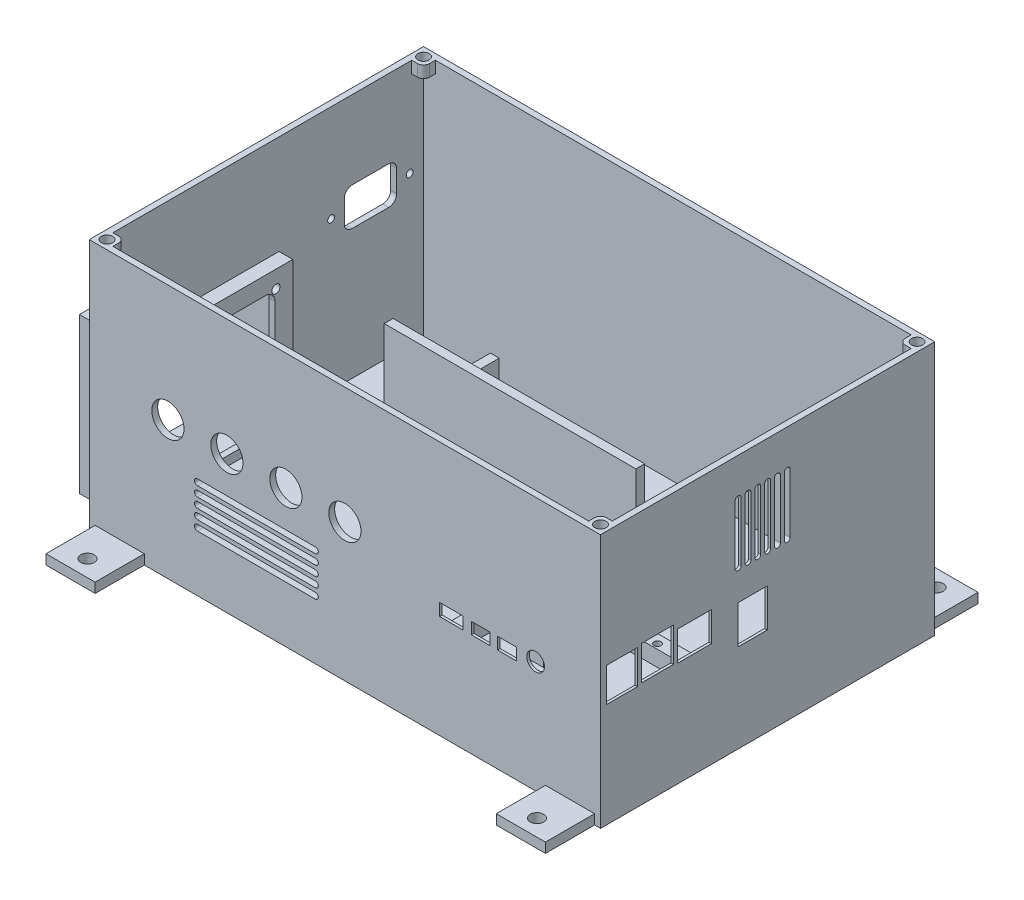
SolidWorks part; units mm, degrees
ref_plane "Front Plane" through (0, 0, 0) normal (0, 0, 1) x (1, 0, 0)
ref_plane "Top Plane" through (0, 0, 0) normal (0, 1, 0) x (1, 0, 0)
ref_plane "Right Plane" through (0, 0, 0) normal (1, 0, 0) x (0, 0, -1)
sketch "Sketch1" plane through (0, 0, 0) normal (0, 1, 0) x (1, 0, 0)
  line L1 (-130, -85) -> (130, -85)
  line L2 (-130, -85) -> (-130, 85)
  line L3 (-130, 85) -> (130, 85)
  line L4 (130, -85) -> (130, 85)
  line L5 (-130, -85) -> (130, 85) construction
  line L6 (-130, 85) -> (130, -85) construction
  point P0 (0, 0)
  dimension "D1" = 170
  dimension "D2" = 260
extrude "Floor" add sketch "Sketch1" along normal blind 4.3805
sketch "Sketch2" plane through (0, 4.3805, 0) normal (0, 1, 0) x (1, 0, 0)
  line L0 (127, -82) -> (127, 82)
  line L1 (127, 82) -> (-127, 82)
  line L2 (-127, 82) -> (-127, -82)
  line L3 (-127, -82) -> (127, -82)
  line L4 (130, -85) -> (130, 85)
  line L5 (130, 85) -> (-130, 85)
  line L6 (-130, 85) -> (-130, -85)
  line L7 (-130, -85) -> (130, -85)
  line L8 (130, -85) -> (130, 85)
  line L9 (130, 85) -> (-130, 85)
  line L10 (-130, 85) -> (-130, -85)
  line L11 (-130, -85) -> (130, -85)
  dimension "D1" = 0
  dimension "D2" = 3
extrude "Wall" add sketch "Sketch2" along normal blind 125
sketch "Sketch4" plane through (0, 4.3805, 0) normal (0, 1, 0) x (1, 0, 0)
  line L0 (120, -33) -> (49, -33)
  line L1 (127, -82) -> (42, -82)
  line L2 (127, -82) -> (127, -26)
  line L3 (127, -26) -> (42, -26)
  line L4 (42, -82) -> (42, -26)
  line L5 (49, -75) -> (49, -33)
  line L6 (120, -75) -> (49, -75)
  line L7 (120, -75) -> (120, -33)
  dimension "D1" = 85
  dimension "D2" = 56
  dimension "D3" = 7
extrude "Rpi stand" add sketch "Sketch4" along normal blind 8 from offset 29
sketch "Sketch7" plane through (0, 129.3805, 0) normal (0, 1, 0) x (1, 0, 0)
sketch "Sketch3" plane through (0, 0, 0) normal (0, 1, 0) x (1, 0, 0)
  line L0 (-114.3, 101.6) -> (114.3, 101.6) construction
  line L1 (-127, 85) -> (-102, 85)
  line L2 (-127, 85) -> (-127, 110)
  line L3 (-127, 110) -> (-102, 110)
  line L4 (-102, 85) -> (-102, 110)
  line L5 (127, 85) -> (102, 85)
  line L6 (127, 85) -> (127, 110)
  line L7 (127, 110) -> (102, 110)
  line L8 (102, 85) -> (102, 110)
  line L9 (-127, -85) -> (-102, -85)
  line L10 (-127, -85) -> (-127, -110)
  line L11 (-127, -110) -> (-102, -110)
  line L12 (-102, -85) -> (-102, -110)
  line L13 (127, -85) -> (102, -85)
  line L14 (127, -85) -> (127, -110)
  line L15 (127, -110) -> (102, -110)
  line L16 (102, -85) -> (102, -110)
  line L17 (114.3, 101.6) -> (114.3, -101.6) construction
  line L18 (114.3, -101.6) -> (-114.3, -101.6) construction
  line L19 (-114.3, -101.6) -> (-114.3, 101.6) construction
  line L20 (-130, 0) -> (130, 0) construction
  line L21 (130, 85) -> (-130, 85) construction
  line L22 (130, -85) -> (130, 85) construction
  line L23 (0, 101.6) -> (0, -101.6) construction
  line L26 (-130, 85) -> (-130, -85) construction
  line L27 (-130, -85) -> (130, -85) construction
  circle A0 centre (-114.3, 101.6) radius 3.429
  circle A1 centre (114.3, 101.6) radius 3.429
  circle A2 centre (114.3, -101.6) radius 3.429
  circle A3 centre (-114.3, -101.6) radius 3.429
  point P4 (-130, -85)
  point P9 (130, -85)
  point P28 (-114.5, -85)
  point P29 (-102, -97.5)
  point P30 (114.5, -85)
  point P31 (-102, 97.5)
  dimension "D5" = 6.858
  dimension "D1" = 25
  dimension "D2" = 25
  dimension "D3" = 25
  dimension "D6" = 203.2
  dimension "D7" = 228.6
  dimension "D8" = 3
  dimension "D9" = 3
  dimension "D4" = 25
extrude "Brackets" add sketch "Sketch3" along normal blind 5
sketch "Sketch5" plane through (-130, 0, 0) normal (-1, 0, 0) x (0, 0, 1)
  line L0 (-8.5, 78.8805) -> (70, 78.8805)
  line L1 (-1, 4.3805) -> (62.5, 4.3805)
  line L2 (-4.5, 7.8805) -> (-4.5, 71.3805)
  line L3 (-1, 74.8805) -> (62.5, 74.8805)
  line L4 (66, 7.8805) -> (66, 71.3805)
  line L5 (70, 0.3805) -> (70, 78.8805)
  line L6 (-8.5, 0.3805) -> (70, 0.3805)
  line L7 (-8.5, 0.3805) -> (-8.5, 78.8805)
  line L8 (-4.5, 4.3805) -> (66, 4.3805) construction
  line L9 (110, 5) -> (110, 0) construction
  line L10 (-4.5, 4.3805) -> (-4.5, 74.8805) construction
  line L11 (-82, 4.3805) -> (82, 4.3805) construction
  line L12 (66, 4.3805) -> (66, 74.8805) construction
  line L13 (-4.5, 74.8805) -> (66, 74.8805) construction
  arc A0 (-1, 4.3805) -> (-4.5, 7.8805) centre (-1, 7.8805) cw
  arc A1 (62.5, 4.3805) -> (66, 7.8805) centre (62.5, 7.8805) ccw
  arc A2 (62.5, 74.8805) -> (66, 71.3805) centre (62.5, 71.3805) cw
  arc A3 (-4.5, 71.3805) -> (-1, 74.8805) centre (-1, 71.3805) cw
  dimension "D4" = 3.5
  dimension "D1" = 70.5
  dimension "D2" = 70.5
  dimension "D5" = 40
  dimension "D3" = 4
extrude "Fan Holder" add sketch "Sketch5" along normal blind 20 and the other way blind 10
sketch "Sketch31" plane through (0, 0.3805, 0) normal (0, -1, 0) x (1, 0, 0)
  line L4 (-130, -8.5) -> (-130, 70)
  line L5 (-130, 70) -> (-150, 70)
  line L6 (-150, 70) -> (-150, -8.5)
  line L7 (-150, -8.5) -> (-130, -8.5)
  line L8 (-130, -8.5) -> (-130, 70)
  line L9 (-130, 70) -> (-150, 70)
  line L10 (-150, 70) -> (-150, -8.5)
  line L11 (-150, -8.5) -> (-130, -8.5)
  dimension "D1" = 0
extrude "Bring fan holder to ground" add sketch "Sketch31" along normal up to surface (0.3805 mm away) up to face at (0, 0, 0)
sketch "Sketch8" plane through (-130, 0, 0) normal (-1, 0, 0) x (0, 0, 1)
  line L4 (-4.5, 71.3805) -> (-4.5, 7.8805)
  line L5 (-1, 4.3805) -> (62.5, 4.3805)
  line L6 (66, 7.8805) -> (66, 71.3805)
  line L7 (62.5, 74.8805) -> (-1, 74.8805)
  line L8 (-4.5, 71.3805) -> (-4.5, 7.8805)
  line L9 (-1, 4.3805) -> (62.5, 4.3805)
  line L10 (66, 7.8805) -> (66, 71.3805)
  line L23 (62.5, 74.8805) -> (-1, 74.8805)
  arc A2 (-4.5, 7.8805) -> (-1, 4.3805) centre (-1, 7.8805) ccw
  arc A3 (-4.5, 7.8805) -> (-1, 4.3805) centre (-1, 7.8805) ccw
  arc A4 (62.5, 4.3805) -> (66, 7.8805) centre (62.5, 7.8805) ccw
  arc A5 (62.5, 4.3805) -> (66, 7.8805) centre (62.5, 7.8805) ccw
  arc A8 (66, 71.3805) -> (62.5, 74.8805) centre (62.5, 71.3805) ccw
  arc A14 (66, 71.3805) -> (62.5, 74.8805) centre (62.5, 71.3805) ccw
  arc A16 (-1, 74.8805) -> (-4.5, 71.3805) centre (-1, 71.3805) ccw
  arc A17 (-1, 74.8805) -> (-4.5, 71.3805) centre (-1, 71.3805) ccw
  dimension "D1" = 0
extrude "Fan hole" cut sketch "Sketch8" against normal up to next
sketch "Sketch11" plane through (-120, 0, 0) normal (-1, 0, 0) x (0, 0, 1)
  line L0 (-8.5, 39.4402) -> (70, 39.4402) construction
  line L1 (30.75, 78.8805) -> (30.75, 0.3805) construction
  line L3 (0.05, 8.7402) -> (61.45, 8.7402) construction
  line L4 (-8.5, 78.8805) -> (-8.5, 0)
  line L5 (-8.5, 0) -> (70, 0)
  line L6 (70, 0) -> (70, 78.8805)
  line L7 (70, 78.8805) -> (-8.5, 78.8805)
  line L8 (-8.5, 78.8805) -> (-8.5, 0)
  line L10 (70, 0) -> (70, 78.8805)
  line L11 (70, 78.8805) -> (-8.5, 78.8805)
  line L12 (0.05, 8.7402) -> (0.05, 70.1402) construction
  line L13 (0.05, 70.1402) -> (61.45, 70.1402) construction
  line L14 (61.45, 8.7402) -> (61.45, 70.1402) construction
  line L15 (0.05, 8.7402) -> (61.45, 70.1402) construction
  line L16 (0.5, 69.8805) -> (0.5, 9)
  line L17 (0.5, 9) -> (61, 9)
  line L18 (61, 9) -> (61, 69.8805)
  line L19 (61, 69.8805) -> (0.5, 69.8805)
  line L20 (0.5, 64.8805) -> (0.5, 14)
  line L22 (61, 14) -> (61, 64.8805)
  line L23 (56, 69.8805) -> (5.5, 69.8805)
  line L24 (0.05, 70.1402) -> (61.45, 8.7402) construction
  line L29 (5.5, 9) -> (56, 9)
  line L31 (-8.5, 0) -> (70, 0)
  arc A0 (0.5, 14) -> (5.5, 9) centre (5.5, 14) ccw
  arc A1 (56, 9) -> (61, 14) centre (56, 14) ccw
  arc A2 (61, 64.8805) -> (56, 69.8805) centre (56, 64.8805) ccw
  arc A3 (0.5, 64.8805) -> (5.5, 69.8805) centre (5.5, 64.8805) cw
  circle A4 centre (0.05, 70.1402) radius 2.1
  circle A5 centre (61.45, 70.1402) radius 2.1
  circle A6 centre (61.45, 8.7402) radius 2.1
  circle A7 centre (0.05, 8.7402) radius 2.1
  point P4 (54.4258, 8.7402)
  point P24 (30.75, 39.4402)
  point P33 (0.5, 21.4808)
  point P34 (30.75, 39.4402)
  point P35 (8.0648, 8.7402)
  point P37 (8.0648, 9.4667)
  point P39 (54.4258, 9.4667)
  dimension "D3" = 5
  dimension "D6" = 4.2
  dimension "D4" = 61.4
  dimension "D5" = 61.4
  dimension "D1" = 0
  dimension "D2" = 9
extrude "Boss-Extrude9" add sketch "Sketch11" along normal blind 3
sketch "Sketch12" plane through (0, 33.3805, 0) normal (0, -1, 0) x (1, 0, 0)
  line L1 (42, 26) -> (49, 26)
  line L2 (42, 26) -> (42, 33)
  line L3 (42, 33) -> (49, 33)
  line L4 (49, 26) -> (49, 33)
  dimension "D1" = 7
  dimension "D2" = 7
extrude "Boss-Extrude10" add sketch "Sketch12" along normal up to next
sketch "Sketch13" plane through (0, 4.3805, 0) normal (0, 1, 0) x (1, 0, 0)
  line L0 (127, 82) -> (-127, 82) construction
  line L2 (-107, -57) -> (-107, 5.7) construction
  line L3 (-107, 5.7) -> (-69.4, 5.7) construction
  line L4 (-107, -57) -> (-69.4, -57) construction
  line L5 (-69.4, 5.7) -> (-69.4, -57) construction
  line L6 (-69.4, 5.7) -> (-57.4, 5.7) construction
  line L7 (-57.4, 5.7) -> (-57.4, -57) construction
  line L8 (-57.4, -57) -> (-19.8, -57) construction
  line L9 (-19.8, -57) -> (-19.8, 5.7) construction
  line L10 (-19.8, 5.7) -> (-57.4, 5.7) construction
  line L11 (-69.4, -57) -> (-57.4, -57) construction
  line L12 (-19.8, -57) -> (62.83, -57) construction
  line L13 (62.83, -57) -> (62.83, -25.4) construction
  line L14 (62.83, -25.4) -> (105, -25.4) construction
  line L15 (105, -25.4) -> (105, -57) construction
  line L16 (105, -57) -> (62.83, -57) construction
  line L17 (118, 82) -> (118, 21.5) construction
  line L18 (-16.3, -57.85) -> (-16.3, 6.55) construction
  line L20 (127, -82) -> (127, 82) construction
  line L21 (118, 21.5) -> (120.7, 21.5) construction
  line L22 (118, 21.5) -> (41.5, 21.5) construction
  line L23 (-6.3, -47) -> (30.69, -47) construction
  line L24 (-6.3, -47) -> (-6.3, -6.4) construction
  line L25 (-6.3, -6.4) -> (30.69, -6.4) construction
  line L26 (30.69, -47) -> (30.69, -6.4) construction
  line L27 (-6.3, -47) -> (30.69, -6.4) construction
  line L28 (-6.3, -6.4) -> (30.69, -47) construction
  line L29 (130, -85) -> (130, 85) construction
  line L30 (-127, -82) -> (127, -82) construction
  line L457 (-127, 8.5) -> (-127, -70) construction
  line L458 (-127, -82) -> (127, -82) construction
  circle A0 centre (-107, -57) radius 1.25
  circle A1 centre (-107, 5.7) radius 1.25
  circle A2 centre (-69.4, 5.7) radius 1.25
  circle A3 centre (-69.4, -57) radius 1.25
  circle A4 centre (-57.4, 5.7) radius 1.25
  circle A5 centre (-57.4, -57) radius 1.25
  circle A6 centre (-19.8, -57) radius 1.25
  circle A7 centre (-19.8, 5.7) radius 1.25
  circle A12 centre (120.7, 21.5) radius 1.25
  circle A13 centre (41.5, 21.5) radius 1.25
  circle A14 centre (-107, 5.7) radius 2.75
  circle A15 centre (-107, -57) radius 2.75
  circle A16 centre (-69.4, 5.7) radius 2.75
  circle A17 centre (-57.4, 5.7) radius 2.75
  circle A18 centre (-69.4, -57) radius 2.75
  circle A19 centre (-57.4, -57) radius 2.75
  circle A20 centre (-19.8, -57) radius 2.75
  circle A21 centre (-19.8, 5.7) radius 2.75
  circle A22 centre (62.83, -57) radius 2.5
  circle A23 centre (62.83, -25.4) radius 2.5
  circle A24 centre (105, -25.4) radius 2.5
  circle A25 centre (105, -57) radius 2.5
  circle A26 centre (-6.3, -47) radius 1.25
  circle A28 centre (-6.3, -47) radius 2.75
  circle A30 centre (-69.4, 5.7) radius 1.65 construction
  circle A31 centre (104.2333, -41.2) radius 1.5 construction
  circle A32 centre (104.2333, -41.2) radius 1.5 construction
  circle A33 centre (63.5933, -41.2) radius 1.5 construction
  circle A34 centre (63.5933, -41.2) radius 1.5 construction
  circle A35 centre (104.2333, -41.2) radius 3
  circle A36 centre (63.5933, -41.2) radius 3
  circle A37 centre (-6.3, -6.4) radius 1.25
  circle A38 centre (30.69, -6.4) radius 1.25
  circle A39 centre (30.69, -47) radius 1.25
  circle A40 centre (-6.3, -6.4) radius 2.75
  circle A41 centre (30.69, -6.4) radius 2.75
  circle A42 centre (30.69, -47) radius 2.75
  circle A43 centre (30.69, -6.4) radius 1.5 construction
  circle A44 centre (30.69, -6.4) radius 1.5 construction
  point P2 (-127, -82)
  point P3 (127, -82)
  point P8 (12.195, -26.7)
  point P31 (127, 82)
  point P32 (-127, 82)
  point P90 (-123, -62.5)
  point P91 (-123, -66)
  point P92 (-130, -70)
  point P93 (-130, 8.5)
  point P94 (-127, 8.5)
  point P95 (-127, -70)
  point P96 (-127, 8.5)
  point P97 (-120, 8.5)
  point P98 (-120, -70)
  point P99 (-127, -70)
  point P100 (-120, 8.5)
  point P101 (-120, -70)
  point P102 (-130, -85)
  point P103 (-127, -85)
  point P104 (-102, -85)
  point P105 (102, -85)
  point P106 (127, -85)
  point P107 (130, -85)
  point P108 (-130, 85)
  point P109 (-130, -85)
  point P110 (130, 85)
  point P111 (127, 85)
  point P112 (102, 85)
  point P113 (-102, 85)
  point P114 (-127, 85)
  point P115 (-130, 85)
  point P116 (130, -85)
  point P117 (130, 85)
  point P118 (-130, 85)
  point P119 (-130, -85)
  point P120 (130, 85)
  point P121 (-130, 85)
  point P122 (130, -85)
  point P123 (130, 85)
  point P124 (-130, -85)
  point P125 (130, -85)
  point P126 (-127, 82)
  point P127 (-127, -82)
  point P128 (127, 82)
  point P129 (-127, 82)
  point P130 (127, -82)
  point P131 (127, 82)
  point P132 (-127, -82)
  point P133 (127, -82)
  point P134 (-127, 82)
  point P135 (-127, 8.5)
  point P136 (-127, -70)
  point P137 (-127, -82)
  point P138 (127, -82)
  point P139 (127, 82)
  point P140 (42, -82)
  point P141 (127, -82)
  point P142 (42, -26)
  point P143 (42, -82)
  point P144 (127, -26)
  point P145 (42, -26)
  point P146 (127, -82)
  point P147 (127, -26)
  point P148 (42, -82)
  point P149 (127, -82)
  point P150 (42, -33)
  point P151 (42, -82)
  point P152 (127, -26)
  point P153 (49, -26)
  point P154 (127, -82)
  point P155 (127, -26)
  point P156 (49, -75)
  point P157 (120, -75)
  point P158 (49, -33)
  point P159 (49, -75)
  point P160 (120, -33)
  point P161 (49, -33)
  point P162 (120, -75)
  point P163 (120, -33)
  point P164 (49, -75)
  point P165 (120, -75)
  point P166 (49, -33)
  point P167 (49, -75)
  point P168 (120, -33)
  point P169 (49, -33)
  point P170 (120, -75)
  point P171 (120, -33)
  point P172 (-102, 110)
  point P173 (-127, 110)
  point P174 (-102, 85)
  point P175 (-102, 110)
  point P176 (-127, 85)
  point P177 (-102, 85)
  point P178 (-127, 110)
  point P179 (-127, 85)
  point P180 (-102, 110)
  point P181 (-127, 110)
  point P182 (-102, 85)
  point P183 (-102, 110)
  point P184 (-127, 110)
  point P185 (-127, 85)
  point P186 (-114.3, 101.6)
  point P187 (-111.0208, 102.6025)
  point P188 (-114.3, 101.6)
  point P189 (-111.0208, 102.6025)
  point P190 (114.3, 101.6)
  point P191 (117.5792, 102.6025)
  point P192 (114.3, 101.6)
  point P193 (117.5792, 102.6025)
  point P194 (127, 85)
  point P195 (127, 110)
  point P196 (127, 110)
  point P197 (102, 110)
  point P198 (102, 110)
  point P199 (102, 85)
  point P200 (127, 85)
  point P201 (127, 110)
  point P202 (127, 110)
  point P203 (102, 110)
  point P204 (102, 110)
  point P205 (102, 85)
  point P206 (102, 85)
  point P207 (127, 85)
  point P208 (-114.3, -101.6)
  point P209 (-111.0208, -100.5975)
  point P210 (-114.3, -101.6)
  point P211 (-111.0208, -100.5975)
  point P212 (-127, -85)
  point P213 (-127, -110)
  point P214 (-127, -110)
  point P215 (-102, -110)
  point P216 (-102, -110)
  point P217 (-102, -85)
  point P218 (-127, -85)
  point P219 (-127, -110)
  point P220 (-127, -110)
  point P221 (-102, -110)
  point P222 (-102, -110)
  point P223 (-102, -85)
  point P224 (-102, -85)
  point P225 (-127, -85)
  point P226 (114.3, -101.6)
  point P227 (117.5792, -100.5975)
  point P228 (114.3, -101.6)
  point P229 (117.5792, -100.5975)
  point P230 (127, -110)
  point P231 (127, -85)
  point P232 (102, -85)
  point P233 (102, -110)
  point P234 (102, -110)
  point P235 (127, -110)
  point P236 (127, -110)
  point P237 (127, -85)
  point P238 (127, -85)
  point P239 (102, -85)
  point P240 (102, -85)
  point P241 (102, -110)
  point P242 (102, -110)
  point P243 (127, -110)
  point P244 (-130, 8.5)
  point P245 (-130, -70)
  point P246 (-120, 8.5)
  point P247 (-127, 8.5)
  point P248 (-130, 8.5)
  point P249 (-150, 8.5)
  point P250 (-120, -70)
  point P251 (-127, -70)
  point P252 (-130, -70)
  point P253 (-150, -70)
  point P254 (-130, -70)
  point P255 (-150, -70)
  point P256 (-130, 8.5)
  point P257 (-150, 8.5)
  point P258 (-120, -70)
  point P259 (-120, 8.5)
  point P260 (-123, 4.5)
  point P261 (-150, 4.5)
  point P262 (-123, 4.5)
  point P263 (-150, 4.5)
  point P264 (-123, 1)
  point P265 (-150, 1)
  point P266 (-123, -62.5)
  point P267 (-150, -62.5)
  point P268 (-123, -66)
  point P269 (-150, -66)
  point P270 (-123, -66)
  point P271 (-150, -66)
  point P272 (-123, -62.5)
  point P273 (-150, -62.5)
  point P274 (-123, 1)
  point P275 (-150, 1)
  point P276 (-150, -70)
  point P277 (-150, 8.5)
  point P278 (-150, 8.5)
  point P279 (-150, -70)
  point P280 (-150, 4.5)
  point P281 (-150, 1)
  point P282 (-150, -62.5)
  point P283 (-150, 1)
  point P284 (-150, -62.5)
  point P285 (-150, -66)
  point P286 (-150, -62.5)
  point P287 (-150, -66)
  point P288 (-150, 1)
  point P289 (-150, -62.5)
  point P290 (-150, 4.5)
  point P291 (-150, 1)
  point P292 (-123, 4.5)
  point P293 (-123, 1)
  point P294 (-123, -62.5)
  point P295 (-123, 1)
  point P296 (-123, 4.5)
  point P297 (-123, 1)
  point P298 (-123, 1)
  point P299 (-123, -62.5)
  point P300 (-123, -62.5)
  point P301 (-123, -66)
  point P302 (-123, -5.5)
  point P303 (-120, -5.5)
  point P304 (-123, -56)
  point P305 (-120, -56)
  point P306 (-123, -61)
  point P307 (-120, -61)
  point P308 (-123, -61)
  point P309 (-120, -61)
  point P310 (-123, -56)
  point P311 (-120, -56)
  point P312 (-123, -5.5)
  point P313 (-120, -5.5)
  point P314 (-123, -0.5)
  point P315 (-120, -0.5)
  point P316 (-123, -0.5)
  point P317 (-120, -0.5)
  point P318 (-123, -0.5)
  point P319 (-123, -5.5)
  point P320 (-123, -56)
  point P321 (-123, -5.5)
  point P322 (-123, -56)
  point P323 (-123, -61)
  point P324 (-123, -56)
  point P325 (-123, -61)
  point P326 (-123, -5.5)
  point P327 (-123, -56)
  point P328 (-123, -0.5)
  point P329 (-123, -5.5)
  point P330 (-120, -5.5)
  point P331 (-120, -0.5)
  point P332 (-120, -56)
  point P333 (-120, -5.5)
  point P334 (-120, -61)
  point P335 (-120, -56)
  point P336 (-120, -61)
  point P337 (-120, -56)
  point P338 (-120, -5.5)
  point P339 (-120, -56)
  point P340 (-120, -5.5)
  point P341 (-120, -0.5)
  point P342 (-123, 2.05)
  point P343 (-123, -2.15)
  point P344 (-120, -2.15)
  point P345 (-120, 2.05)
  point P346 (-123, -59.35)
  point P347 (-123, -63.55)
  point P348 (-120, -63.55)
  point P349 (-120, -59.35)
  point P350 (-123, -59.35)
  point P351 (-123, -63.55)
  point P352 (-120, -63.55)
  point P353 (-120, -59.35)
  point P354 (-123, 2.05)
  point P355 (-123, -2.15)
  point P356 (-120, -2.15)
  point P357 (-120, 2.05)
  point P358 (49, -33)
  point P359 (42, -33)
  point P360 (49, -26)
  point P361 (49, -33)
  point P362 (42, -33)
  point P363 (42, -26)
  point P364 (42, -26)
  point P365 (49, -26)
  point P366 (49, -26)
  point P367 (49, -33)
  point P368 (49, -33)
  point P369 (42, -33)
  point P370 (-130, -85)
  point P371 (130, -85)
  point P372 (-130, -85)
  point P373 (-130, 85)
  point P374 (-130, 85)
  point P375 (130, 85)
  point P376 (130, -85)
  point P377 (130, 85)
  point P378 (-130, -85)
  point P379 (130, 85)
  point P380 (-130, 85)
  point P381 (130, -85)
  point P382 (127, -82)
  point P383 (127, 82)
  point P384 (127, 82)
  point P385 (-127, 82)
  point P386 (-127, 82)
  point P387 (-127, -82)
  point P388 (-127, -82)
  point P389 (127, -82)
  point P390 (130, -85)
  point P391 (130, 85)
  point P392 (130, 85)
  point P393 (-130, 85)
  point P394 (-130, 85)
  point P395 (-130, -85)
  point P396 (-130, -85)
  point P397 (130, -85)
  point P398 (130, -85)
  point P399 (130, 85)
  point P400 (130, 85)
  point P401 (-130, 85)
  point P402 (-130, 85)
  point P403 (-130, -85)
  point P404 (-130, -85)
  point P405 (130, -85)
  point P406 (120, -33)
  point P407 (49, -33)
  point P408 (127, -82)
  point P409 (42, -82)
  point P410 (127, -82)
  point P411 (127, -26)
  point P412 (127, -26)
  point P413 (42, -26)
  point P414 (42, -82)
  point P415 (42, -26)
  point P416 (49, -75)
  point P417 (49, -33)
  point P418 (120, -75)
  point P419 (49, -75)
  point P420 (120, -75)
  point P421 (120, -33)
  point P422 (-114.3, 101.6)
  point P423 (114.3, 101.6)
  point P424 (-127, 85)
  point P425 (-102, 85)
  point P426 (-127, 85)
  point P427 (-127, 110)
  point P428 (-127, 110)
  point P429 (-102, 110)
  point P430 (-102, 85)
  point P431 (-102, 110)
  point P432 (127, 85)
  point P433 (102, 85)
  point P434 (127, 85)
  point P435 (127, 110)
  point P436 (127, 110)
  point P437 (102, 110)
  point P438 (102, 85)
  point P439 (102, 110)
  point P440 (-127, -85)
  point P441 (-102, -85)
  point P442 (-127, -85)
  point P443 (-127, -110)
  point P444 (-127, -110)
  point P445 (-102, -110)
  point P446 (-102, -85)
  point P447 (-102, -110)
  point P448 (127, -85)
  point P449 (102, -85)
  point P450 (127, -85)
  point P451 (127, -110)
  point P452 (127, -110)
  point P453 (102, -110)
  point P454 (102, -85)
  point P455 (102, -110)
  point P456 (114.3, 101.6)
  point P457 (114.3, -101.6)
  point P458 (114.3, -101.6)
  point P459 (-114.3, -101.6)
  point P460 (-114.3, -101.6)
  point P461 (-114.3, 101.6)
  point P462 (-130, 0)
  point P463 (130, 0)
  point P464 (130, 85)
  point P465 (-130, 85)
  point P466 (130, -85)
  point P467 (130, 85)
  point P468 (0, 101.6)
  point P469 (0, -101.6)
  point P470 (-130, 85)
  point P471 (-130, -85)
  point P472 (-130, -85)
  point P473 (130, -85)
  point P474 (-130, 8.5)
  point P475 (-130, -70)
  point P476 (-130, 1)
  point P477 (-130, -62.5)
  point P478 (-130, 1)
  point P479 (-130, -62.5)
  point P480 (-130, 8.5)
  point P481 (-130, -70)
  point P482 (-130, 4.5)
  point P483 (-130, -66)
  point P484 (-130, 82)
  point P485 (-130, -82)
  point P486 (-130, 4.5)
  point P487 (-130, -66)
  point P488 (-130, 1)
  point P489 (-130, -62.5)
  point P490 (-130, -62.5)
  point P491 (-130, 1)
  point P492 (-130, 1)
  point P493 (-130, -62.5)
  point P494 (-130, -62.5)
  point P495 (-130, 1)
  point P496 (-120, 8.5)
  point P497 (-120, -70)
  point P498 (-120, -0.05)
  point P499 (-120, -61.45)
  point P500 (-120, 8.5)
  point P501 (-120, -70)
  point P502 (-120, -70)
  point P503 (-120, 8.5)
  point P504 (-120, 8.5)
  point P505 (-120, -70)
  point P506 (-120, -70)
  point P507 (-120, 8.5)
  point P508 (-120, -0.05)
  point P509 (-120, -61.45)
  point P510 (-120, -0.05)
  point P511 (-120, -61.45)
  point P512 (-120, -0.5)
  point P513 (-120, -61)
  point P514 (-120, -61)
  point P515 (-120, -0.5)
  point P516 (-120, -5.5)
  point P517 (-120, -56)
  point P518 (-120, -56)
  point P519 (-120, -5.5)
  point P520 (-120, -0.05)
  point P521 (-120, -61.45)
  point P522 (42, -26)
  point P523 (49, -26)
  point P524 (42, -26)
  point P525 (42, -33)
  point P526 (42, -33)
  point P527 (49, -33)
  point P528 (49, -26)
  point P529 (49, -33)
  point P530 (-123, -62.5)
  point P531 (-123, -66)
  point P532 (-130, -70)
  point P533 (-130, 8.5)
  point P534 (-127, 8.5)
  point P535 (-127, -70)
  point P536 (-127, 8.5)
  point P537 (-120, 8.5)
  point P538 (-120, -70)
  point P539 (-127, -70)
  point P540 (-120, 8.5)
  point P541 (-120, -70)
  point P542 (-130, -85)
  point P543 (-127, -85)
  point P544 (-102, -85)
  point P545 (102, -85)
  point P546 (127, -85)
  point P547 (130, -85)
  point P548 (-130, 85)
  point P549 (-130, -85)
  point P550 (130, 85)
  point P551 (127, 85)
  point P552 (102, 85)
  point P553 (-102, 85)
  point P554 (-127, 85)
  point P555 (-130, 85)
  point P556 (130, -85)
  point P557 (130, 85)
  point P558 (-130, 85)
  point P559 (-130, -85)
  point P560 (130, 85)
  point P561 (-130, 85)
  point P562 (130, -85)
  point P563 (130, 85)
  point P564 (-130, -85)
  point P565 (130, -85)
  point P566 (-127, 82)
  point P567 (-127, -82)
  point P568 (127, 82)
  point P569 (-127, 82)
  point P570 (127, -82)
  point P571 (127, 82)
  point P572 (-127, -82)
  point P573 (127, -82)
  point P574 (-127, 82)
  point P575 (-127, 8.5)
  point P576 (-127, -70)
  point P577 (-127, -82)
  point P578 (127, 82)
  point P579 (-127, 82)
  point P580 (127, -82)
  point P581 (127, 82)
  point P582 (-127, -82)
  point P583 (127, -82)
  point P584 (42, -82)
  point P585 (127, -82)
  point P586 (42, -26)
  point P587 (42, -82)
  point P588 (127, -26)
  point P589 (42, -26)
  point P590 (127, -82)
  point P591 (127, -26)
  point P592 (42, -82)
  point P593 (127, -82)
  point P594 (42, -33)
  point P595 (42, -82)
  point P596 (127, -26)
  point P597 (49, -26)
  point P598 (127, -82)
  point P599 (127, -26)
  point P600 (49, -75)
  point P601 (120, -75)
  point P602 (49, -33)
  point P603 (49, -75)
  point P604 (120, -33)
  point P605 (49, -33)
  point P606 (120, -75)
  point P607 (120, -33)
  point P608 (49, -75)
  point P609 (120, -75)
  point P610 (49, -33)
  point P611 (49, -75)
  point P612 (120, -33)
  point P613 (49, -33)
  point P614 (120, -75)
  point P615 (120, -33)
  point P616 (-102, 110)
  point P617 (-127, 110)
  point P618 (-102, 85)
  point P619 (-102, 110)
  point P620 (-127, 85)
  point P621 (-102, 85)
  point P622 (-127, 110)
  point P623 (-127, 85)
  point P624 (-102, 110)
  point P625 (-127, 110)
  point P626 (-102, 85)
  point P627 (-102, 110)
  point P628 (-127, 110)
  point P629 (-127, 85)
  point P630 (-114.3, 101.6)
  point P631 (-111.0208, 102.6025)
  point P632 (-114.3, 101.6)
  point P633 (-111.0208, 102.6025)
  point P634 (114.3, 101.6)
  point P635 (117.5792, 102.6025)
  point P636 (114.3, 101.6)
  point P637 (117.5792, 102.6025)
  point P638 (127, 85)
  point P639 (127, 110)
  point P640 (127, 110)
  point P641 (102, 110)
  point P642 (102, 110)
  point P643 (102, 85)
  point P644 (127, 85)
  point P645 (127, 110)
  point P646 (127, 110)
  point P647 (102, 110)
  point P648 (102, 110)
  point P649 (102, 85)
  point P650 (102, 85)
  point P651 (127, 85)
  point P652 (-114.3, -101.6)
  point P653 (-111.0208, -100.5975)
  point P654 (-114.3, -101.6)
  point P655 (-111.0208, -100.5975)
  point P656 (-127, -85)
  point P657 (-127, -110)
  point P658 (-127, -110)
  point P659 (-102, -110)
  point P660 (-102, -110)
  point P661 (-102, -85)
  point P662 (-127, -85)
  point P663 (-127, -110)
  point P664 (-127, -110)
  point P665 (-102, -110)
  point P666 (-102, -110)
  point P667 (-102, -85)
  point P668 (-102, -85)
  point P669 (-127, -85)
  point P670 (114.3, -101.6)
  point P671 (117.5792, -100.5975)
  point P672 (114.3, -101.6)
  point P673 (117.5792, -100.5975)
  point P674 (127, -110)
  point P675 (127, -85)
  point P676 (102, -85)
  point P677 (102, -110)
  point P678 (102, -110)
  point P679 (127, -110)
  point P680 (127, -110)
  point P681 (127, -85)
  point P682 (127, -85)
  point P683 (102, -85)
  point P684 (102, -85)
  point P685 (102, -110)
  point P686 (102, -110)
  point P687 (127, -110)
  point P688 (-130, 8.5)
  point P689 (-130, -70)
  point P690 (-120, 8.5)
  point P691 (-127, 8.5)
  point P692 (-130, 8.5)
  point P693 (-150, 8.5)
  point P694 (-120, -70)
  point P695 (-127, -70)
  point P696 (-130, -70)
  point P697 (-150, -70)
  point P698 (-130, -70)
  point P699 (-150, -70)
  point P700 (-130, 8.5)
  point P701 (-150, 8.5)
  point P702 (-120, -70)
  point P703 (-120, 8.5)
  point P704 (-123, 4.5)
  point P705 (-150, 4.5)
  point P706 (-123, 4.5)
  point P707 (-150, 4.5)
  point P708 (-123, 1)
  point P709 (-150, 1)
  point P710 (-123, -62.5)
  point P711 (-150, -62.5)
  point P712 (-123, -66)
  point P713 (-150, -66)
  point P714 (-123, -66)
  point P715 (-150, -66)
  point P716 (-123, -62.5)
  point P717 (-150, -62.5)
  point P718 (-123, 1)
  point P719 (-150, 1)
  point P720 (-150, -70)
  point P721 (-150, 8.5)
  point P722 (-150, 8.5)
  point P723 (-150, -70)
  point P724 (-150, 4.5)
  point P725 (-150, 1)
  point P726 (-150, -62.5)
  point P727 (-150, 1)
  point P728 (-150, -62.5)
  point P729 (-150, -66)
  point P730 (-150, -62.5)
  point P731 (-150, -66)
  point P732 (-150, 1)
  point P733 (-150, -62.5)
  point P734 (-150, 4.5)
  point P735 (-150, 1)
  point P736 (-123, 4.5)
  point P737 (-123, 1)
  point P738 (-123, -62.5)
  point P739 (-123, 1)
  point P740 (-123, 4.5)
  point P741 (-123, 1)
  point P742 (-123, 1)
  point P743 (-123, -62.5)
  point P744 (-123, -62.5)
  point P745 (-123, -66)
  point P746 (-123, -5.5)
  point P747 (-120, -5.5)
  point P748 (-123, -56)
  point P749 (-120, -56)
  point P750 (-123, -61)
  point P751 (-120, -61)
  point P752 (-123, -61)
  point P753 (-120, -61)
  point P754 (-123, -56)
  point P755 (-120, -56)
  point P756 (-123, -5.5)
  point P757 (-120, -5.5)
  point P758 (-123, -0.5)
  point P759 (-120, -0.5)
  point P760 (-123, -0.5)
  point P761 (-120, -0.5)
  point P762 (-123, -0.5)
  point P763 (-123, -5.5)
  point P764 (-123, -56)
  point P765 (-123, -5.5)
  point P766 (-123, -56)
  point P767 (-123, -61)
  point P768 (-123, -56)
  point P769 (-123, -61)
  point P770 (-123, -5.5)
  point P771 (-123, -56)
  point P772 (-123, -0.5)
  point P773 (-123, -5.5)
  point P774 (-120, -5.5)
  point P775 (-120, -0.5)
  point P776 (-120, -56)
  point P777 (-120, -5.5)
  point P778 (-120, -61)
  point P779 (-120, -56)
  point P780 (-120, -61)
  point P781 (-120, -56)
  point P782 (-120, -5.5)
  point P783 (-120, -56)
  point P784 (-120, -5.5)
  point P785 (-120, -0.5)
  point P786 (-123, 2.05)
  point P787 (-123, -2.15)
  point P788 (-120, -2.15)
  point P789 (-120, 2.05)
  point P790 (-123, -59.35)
  point P791 (-123, -63.55)
  point P792 (-120, -63.55)
  point P793 (-120, -59.35)
  point P794 (-123, -59.35)
  point P795 (-123, -63.55)
  point P796 (-120, -63.55)
  point P797 (-120, -59.35)
  point P798 (-123, 2.05)
  point P799 (-123, -2.15)
  point P800 (-120, -2.15)
  point P801 (-120, 2.05)
  point P802 (49, -33)
  point P803 (42, -33)
  point P804 (49, -26)
  point P805 (49, -33)
  point P806 (42, -33)
  point P807 (42, -26)
  point P808 (42, -26)
  point P809 (49, -26)
  point P810 (49, -26)
  point P811 (49, -33)
  point P812 (49, -33)
  point P813 (42, -33)
  point P814 (-130, -85)
  point P815 (130, -85)
  point P816 (-130, -85)
  point P817 (-130, 85)
  point P818 (-130, 85)
  point P819 (130, 85)
  point P820 (130, -85)
  point P821 (130, 85)
  point P822 (-130, -85)
  point P823 (130, 85)
  point P824 (-130, 85)
  point P825 (130, -85)
  point P826 (127, -82)
  point P827 (127, 82)
  point P828 (127, 82)
  point P829 (-127, 82)
  point P830 (-127, 82)
  point P831 (-127, -82)
  point P832 (-127, -82)
  point P833 (127, -82)
  point P834 (130, -85)
  point P835 (130, 85)
  point P836 (130, 85)
  point P837 (-130, 85)
  point P838 (-130, 85)
  point P839 (-130, -85)
  point P840 (-130, -85)
  point P841 (130, -85)
  point P842 (130, -85)
  point P843 (130, 85)
  point P844 (130, 85)
  point P845 (-130, 85)
  point P846 (-130, 85)
  point P847 (-130, -85)
  point P848 (-130, -85)
  point P849 (130, -85)
  point P850 (120, -33)
  point P851 (49, -33)
  point P852 (127, -82)
  point P853 (42, -82)
  point P854 (127, -82)
  point P855 (127, -26)
  point P856 (127, -26)
  point P857 (42, -26)
  point P858 (42, -82)
  point P859 (42, -26)
  point P860 (49, -75)
  point P861 (49, -33)
  point P862 (120, -75)
  point P863 (49, -75)
  point P864 (120, -75)
  point P865 (120, -33)
  point P866 (-114.3, 101.6)
  point P867 (114.3, 101.6)
  point P868 (-127, 85)
  point P869 (-102, 85)
  point P870 (-127, 85)
  point P871 (-127, 110)
  point P872 (-127, 110)
  point P873 (-102, 110)
  point P874 (-102, 85)
  point P875 (-102, 110)
  point P876 (127, 85)
  point P877 (102, 85)
  point P878 (127, 85)
  point P879 (127, 110)
  point P880 (127, 110)
  point P881 (102, 110)
  point P882 (102, 85)
  point P883 (102, 110)
  point P884 (-127, -85)
  point P885 (-102, -85)
  point P886 (-127, -85)
  point P887 (-127, -110)
  point P888 (-127, -110)
  point P889 (-102, -110)
  point P890 (-102, -85)
  point P891 (-102, -110)
  point P892 (127, -85)
  point P893 (102, -85)
  point P894 (127, -85)
  point P895 (127, -110)
  point P896 (127, -110)
  point P897 (102, -110)
  point P898 (102, -85)
  point P899 (102, -110)
  point P900 (114.3, 101.6)
  point P901 (114.3, -101.6)
  point P902 (114.3, -101.6)
  point P903 (-114.3, -101.6)
  point P904 (-114.3, -101.6)
  point P905 (-114.3, 101.6)
  point P906 (-130, 0)
  point P907 (130, 0)
  point P908 (130, 85)
  point P909 (-130, 85)
  point P910 (130, -85)
  point P911 (130, 85)
  point P912 (0, 101.6)
  point P913 (0, -101.6)
  point P914 (-130, 85)
  point P915 (-130, -85)
  point P916 (-130, -85)
  point P917 (130, -85)
  point P918 (-130, 8.5)
  point P919 (-130, -70)
  point P920 (-130, 1)
  point P921 (-130, -62.5)
  point P922 (-130, 1)
  point P923 (-130, -62.5)
  point P924 (-130, 8.5)
  point P925 (-130, -70)
  point P926 (-130, 4.5)
  point P927 (-130, -66)
  point P928 (-130, 82)
  point P929 (-130, -82)
  point P930 (-130, 4.5)
  point P931 (-130, -66)
  point P932 (-130, 1)
  point P933 (-130, -62.5)
  point P934 (-130, -62.5)
  point P935 (-130, 1)
  point P936 (-130, 1)
  point P937 (-130, -62.5)
  point P938 (-130, -62.5)
  point P939 (-130, 1)
  point P940 (-120, 8.5)
  point P941 (-120, -70)
  point P942 (-120, -0.05)
  point P943 (-120, -61.45)
  point P944 (-120, 8.5)
  point P945 (-120, -70)
  point P946 (-120, -70)
  point P947 (-120, 8.5)
  point P948 (-120, 8.5)
  point P949 (-120, -70)
  point P950 (-120, -70)
  point P951 (-120, 8.5)
  point P952 (-120, -0.05)
  point P953 (-120, -61.45)
  point P954 (-120, -0.05)
  point P955 (-120, -61.45)
  point P956 (-120, -0.5)
  point P957 (-120, -61)
  point P958 (-120, -61)
  point P959 (-120, -0.5)
  point P960 (-120, -5.5)
  point P961 (-120, -56)
  point P962 (-120, -56)
  point P963 (-120, -5.5)
  point P964 (-120, -0.05)
  point P965 (-120, -61.45)
  point P966 (42, -26)
  point P967 (49, -26)
  point P968 (42, -26)
  point P969 (42, -33)
  point P970 (42, -33)
  point P971 (49, -33)
  point P972 (49, -26)
  point P973 (49, -33)
  dimension "D3" = 2.5
  dimension "D6" = 1.5
  dimension "D7" = 2.5
  dimension "D8" = 10
  dimension "D11" = 35
  dimension "D12" = 20
  dimension "D13" = 25
  dimension "D25" = 2.5
  dimension "D27" = 2.5
  dimension "D4" = 5
  dimension "D5" = 25
  dimension "D9" = 12
  dimension "D10" = 1.5
  dimension "D17" = 31.6
  dimension "D19" = 42.17
  dimension "D22" = 60.5
  dimension "D23" = 9
  dimension "D24" = 2.7
  dimension "D26" = 76.5
  dimension "D28" = 1.5
extrude "Built in Standoffs" add sketch "Sketch13" along normal blind 5 contours A1 | A16 A2 | A2 | A17 A4 | A4 | A14 A1 | A21 A7 | A7 | A15 A0 | A0 | A18 A3 | A3 | A19 A5 | A5 | A20 A6 | A6 | A22 | A23 | A24 A32 | A32 | A25 | A36 | A35 | A28 A26 | A26 | A40 A37 | A37 | A41 A38 | A38 | A42 A39 | A39 region at (-107, 4.3805, 57) region at (-107, 4.3805, -5.7) region at (-69.4, 4.3805, -5.7) region at (-69.4, 4.3805, 57) region at (-57.4, 4.3805, -5.7) region at (-57.4, 4.3805, 57) region at (-19.8, 4.3805, 57) region at (-19.8, 4.3805, -5.7) region at (-109.6722, 4.3805, -5.7) region at (-109.6722, 4.3805, 57) region at (-72.0722, 4.3805, -5.7) region at (-60.0722, 4.3805, -5.7) region at (-72.0722, 4.3805, 57) region at (-60.0722, 4.3805, 57) region at (-22.4722, 4.3805, 57) region at (-22.4722, 4.3805, -5.7) region at (62.83, 4.3805, 57) region at (62.83, 4.3805, 25.4) region at (105, 4.3805, 25.4) region at (105, 4.3805, 57) region at (-6.3, 4.3805, 47) region at (-8.9722, 4.3805, 47) region at (104.2333, 4.3805, 41.2) region at (63.5933, 4.3805, 41.2) region at (-6.3, 4.3805, 6.4) region at (30.69, 4.3805, 6.4) region at (30.69, 4.3805, 47) region at (-8.9722, 4.3805, 6.4) region at (28.0178, 4.3805, 6.4) region at (28.0178, 4.3805, 47)
sketch "Sketch19" plane through (0, 9.3805, 0) normal (0, 1, 0) x (1, 0, 0)
  circle A0 centre (104.2333, -41.2) radius 1.25
  circle A1 centre (63.5933, -41.2) radius 1.25
  dimension "D1" = 2.5
  dimension "D2" = 2.5
extrude "Bread board holes" cut sketch "Sketch19" against normal blind 7
sketch "Sketch14" plane through (0, 4.3805, 0) normal (0, 1, 0) x (1, 0, 0)
  line L0 (127, 82) -> (-88, 82)
  line L1 (127, 82) -> (-127, 82) construction
  line L2 (-88, 82) -> (-88, 32)
  line L3 (-88, 32) -> (127, 32)
  line L4 (127, -82) -> (127, 82) construction
  line L5 (127, 32) -> (127, 82)
  dimension "D1" = 215
  dimension "D2" = 50
extrude "Screw Holes" cut sketch "Sketch13<4>" against normal blind 7 from surface contours A37 | A38 | A26 | A39 | A1 | A0 | A3 | A5 | A2 | A4 | A7 | A6 | A32 region at (-6.3, 4.3805, 47) region at (-6.3, 4.3805, 6.4) region at (30.69, 4.3805, 6.4) region at (30.69, 4.3805, 47) starting at face at (-107, 9.3805, -2.95)
sketch "Sketch13<4>" plane through (0, 4.3805, 0) normal (0, 1, 0) x (1, 0, 0) same geometry as "Sketch13"
extrude "Driver Screw Holes" cut sketch "Sketch13<5>" against normal blind 3 contours A13 | A12
sketch "Sketch13<5>" plane through (0, 4.3805, 0) normal (0, 1, 0) x (1, 0, 0) same geometry as "Sketch13"
sketch "Sketch16" plane through (0, 4.3805, 0) normal (0, 1, 0) x (1, 0, 0)
  line L0 (-93, 82) -> (-93, 28)
  line L1 (-93, 28) -> (35, 28)
  line L2 (-88.5, 82) -> (-88.5, 32.5)
  line L3 (-88.5, 32.5) -> (35, 32.5)
  line L10 (-88, 82) -> (-88, 33) construction
  line L11 (-88, 33) -> (29.1074, 33) construction
  line L14 (-93, 28) -> (127, 28) construction
  line L16 (-88, 33) -> (127, 33) construction
  line L17 (-88.5, 82) -> (-93, 82)
  line L20 (35, 28) -> (35, 32.5)
  line L21 (-88.5, 32.5) -> (29.1074, 32.5) construction
  line L25 (-88, 33) -> (127, 33)
  line L26 (127, 33) -> (127, 82)
  line L27 (127, 82) -> (-88, 82)
  line L28 (-88, 82) -> (-88, 33)
  line L29 (-88, 33) -> (127, 33) construction
  line L30 (127, 33) -> (127, 82) construction
  line L31 (127, 82) -> (-88, 82) construction
  line L32 (-88, 82) -> (-88, 33) construction
  line L57 (-88, 82) -> (-88, 33) construction
  line L58 (127, 82) -> (-127, 82) construction
  dimension "D3" = 0.5
  dimension "D5" = 128
  dimension "D1" = 0
  dimension "D2" = 5
extrude "Power supply wall" add sketch "Sketch16" along normal blind 10 contours L2 L3 L20 L1 L0 L17
sketch "Sketch25" plane through (0, 14.3805, 0) normal (0, 1, 0) x (1, 0, 0)
  line L0 (-93, 82) -> (-93, 28) construction
  line L1 (35, 28) -> (-93, 28)
  line L2 (35, 28) -> (35, 32.5)
  line L3 (35, 32.5) -> (-93, 32.5)
  line L4 (-93, 28) -> (-93, 32.5)
  line L5 (-88.5, 32.5) -> (35, 32.5) construction
  line L6 (-88.5, 32.5) -> (35, 32.5) construction
extrude "Boss-Extrude11" add sketch "Sketch25" along normal blind 40
sketch "Sketch17" plane through (0, 41.3805, 0) normal (0, 1, 0) x (1, 0, 0)
  circle A0 centre (46.5, -30.5) radius 1.7859
  circle A1 centre (104.5, -30.5) radius 1.7859
  circle A2 centre (104.5, -79.5) radius 1.7859
  circle A3 centre (46.5, -79.5) radius 1.7859
  dimension "D1" = 3.5719
extrude "rpi standoff holes" cut sketch "Sketch17" against normal blind 6
sketch "Sketch20" plane through (0, 0, 85) normal (0, 0, 1) x (1, 0, 0)
  line L1 (49.6827, 57.1504) -> (58.6882, 57.1504) construction
  line L2 (49.6827, 57.1504) -> (49.6827, 53.9554) construction
  line L3 (49.6827, 53.9554) -> (58.6882, 53.9554) construction
  line L4 (58.6882, 57.1504) -> (58.6882, 53.9554) construction
  line L5 (79.2167, 56.9908) -> (85.8798, 56.9908) construction
  line L6 (79.2167, 56.9908) -> (79.2167, 53.9258) construction
  line L7 (79.2167, 53.9258) -> (85.8798, 53.9258) construction
  line L8 (85.8798, 56.9908) -> (85.8798, 53.9258) construction
  line L9 (65.7798, 56.9112) -> (72.2962, 56.9112) construction
  line L10 (65.7798, 56.9112) -> (65.7798, 53.9475) construction
  line L11 (65.7798, 53.9475) -> (72.2962, 53.9475) construction
  line L12 (72.2962, 56.9112) -> (72.2962, 53.9475) construction
  line L13 (48.1827, 58.6504) -> (60.1882, 58.6504)
  line L14 (60.1882, 58.6504) -> (60.1882, 52.4554)
  line L15 (48.1827, 52.4554) -> (60.1882, 52.4554)
  line L16 (48.1827, 58.6504) -> (48.1827, 52.4554)
  line L17 (77.7167, 58.4908) -> (87.3798, 58.4908)
  line L18 (87.3798, 58.4908) -> (87.3798, 52.4258)
  line L19 (77.7167, 52.4258) -> (87.3798, 52.4258)
  line L20 (77.7167, 58.4908) -> (77.7167, 52.4258)
  line L21 (64.2798, 58.4112) -> (73.7962, 58.4112)
  line L22 (73.7962, 58.4112) -> (73.7962, 52.4475)
  line L23 (64.2798, 52.4475) -> (73.7962, 52.4475)
  line L24 (64.2798, 58.4112) -> (64.2798, 52.4475)
  circle A0 centre (97, 56.9705) radius 4.5
  dimension "D1" = 9
  dimension "D2" = 1.5
extrude "Cut-Extrude5" cut sketch "Sketch20" against normal up to next
sketch "Sketch21" plane through (0, 129.3805, 0) normal (0, 1, 0) x (1, 0, 0)
  line L0 (125, -26.3) -> (46, -26.3) construction
  line L1 (42.3, -30) -> (42.3, -80) construction
  line L2 (46, -83.7) -> (125, -83.7)
  line L3 (128.7, -80) -> (128.7, -30)
  line L4 (128, -80) -> (128, -30)
  line L5 (125, -27) -> (46, -27)
  line L6 (43, -30) -> (43, -80)
  line L7 (46, -83) -> (125, -83)
  line L8 (128, -80) -> (128, -30) construction
  line L9 (125, -27) -> (46, -27) construction
  line L10 (43, -30) -> (43, -80) construction
  line L11 (46, -83) -> (125, -83) construction
  line L28 (46, -83.7) -> (20.659, -83.7)
  line L29 (20.659, -83.7) -> (20.659, 4.3626)
  line L30 (20.659, 4.3626) -> (128.7, 4.3626)
  line L31 (128.7, 4.3626) -> (128.7, -30)
  arc A0 (46, -26.3) -> (42.3, -30) centre (46, -30) ccw construction
  arc A1 (42.3, -80) -> (46, -83.7) centre (46, -80) ccw construction
  arc A2 (125, -83.7) -> (128.7, -80) centre (125, -80) ccw
  arc A3 (128.7, -30) -> (125, -26.3) centre (125, -30) ccw construction
  arc A4 (128, -30) -> (125, -27) centre (125, -30) ccw
  arc A5 (46, -27) -> (43, -30) centre (46, -30) ccw
  arc A6 (43, -80) -> (46, -83) centre (46, -80) ccw
  arc A7 (125, -83) -> (128, -80) centre (125, -80) ccw
  arc A8 (128, -30) -> (125, -27) centre (125, -30) ccw construction
  arc A9 (46, -27) -> (43, -30) centre (46, -30) ccw construction
  arc A10 (43, -80) -> (46, -83) centre (46, -80) ccw construction
  arc A11 (125, -83) -> (128, -80) centre (125, -80) ccw construction
  dimension "D1" = 0
  dimension "D2" = 0.7
extrude "Rpi Room" cut sketch "Sketch21" against normal up to surface (88 mm away) from offset 20 contours L2 A2 L3 L31 L30 L29 L28 up to face at (46.5, 41.3805, 81.2859) offset against normal yes
sketch "Sketch22" plane through (130, 0, 0) normal (1, 0, 0) x (0, 0, -1)
  line L0 (-81.966, 70.2905) -> (-66.1499, 70.2905)
  line L1 (-81.166, 69.4905) -> (-66.9499, 69.4905) construction
  line L2 (-81.166, 69.4905) -> (-81.166, 53.8427) construction
  line L3 (-81.166, 53.8427) -> (-66.9499, 53.8427) construction
  line L4 (-66.9499, 69.4905) -> (-66.9499, 53.8427) construction
  line L5 (-63.3011, 70.2905) -> (-48.6526, 70.2905) construction
  line L6 (-63.3011, 70.2905) -> (-63.3011, 54.5222) construction
  line L7 (-63.3011, 54.5222) -> (-48.6526, 54.5222) construction
  line L8 (-48.6526, 70.2905) -> (-48.6526, 54.5222) construction
  line L9 (-45.1414, 67.4119) -> (-29.3586, 67.4119) construction
  line L10 (-45.1414, 67.4119) -> (-45.1414, 53.9605) construction
  line L11 (-45.1414, 53.9605) -> (-29.3586, 53.9605) construction
  line L12 (-29.3586, 67.4119) -> (-29.3586, 53.9605) construction
  line L13 (-66.1499, 70.2905) -> (-66.1499, 53.0427)
  line L14 (-81.966, 53.0427) -> (-66.1499, 53.0427)
  line L15 (-81.966, 70.2905) -> (-81.966, 53.0427)
  line L16 (-64.1011, 71.0905) -> (-47.8526, 71.0905)
  line L17 (-47.8526, 71.0905) -> (-47.8526, 53.7222)
  line L18 (-64.1011, 53.7222) -> (-47.8526, 53.7222)
  line L19 (-64.1011, 71.0905) -> (-64.1011, 53.7222)
  line L20 (-45.9414, 68.2119) -> (-28.5586, 68.2119)
  line L21 (-28.5586, 68.2119) -> (-28.5586, 53.1605)
  line L22 (-45.9414, 53.1605) -> (-28.5586, 53.1605)
  line L23 (-45.9414, 68.2119) -> (-45.9414, 53.1605)
  line L24 (-70.9672, 69.4905) -> (-73.95, 69.4905) construction
  line L25 (-85, 129.3805) -> (-85, 0) construction
  line L26 (-85, 0) -> (85, 0) construction
  arc A0 (-29.3, 67.2705) -> (-29.5, 67.4705) centre (-29.5, 67.2705) ccw construction
  dimension "D2" = 3.834
  dimension "D3" = 14.2161
  dimension "D4" = 15.6478
  dimension "D5" = 3.6488
  dimension "D6" = 14.6485
  dimension "D7" = 15.7683
  dimension "D8" = 70.2905
  dimension "D9" = 13.4514
  dimension "D1" = 0.8
extrude "Cut-Extrude7" cut sketch "Sketch22" against normal up to next
sketch "Sketch24" plane through (0, 0, -85) normal (0, 0, -1) x (-1, 0, 0)
  circle A0 centre (-93.2948, 35.78) radius 16.8996 construction
  circle A1 centre (-93.2948, 35.78) radius 16.8996 construction
  circle A2 centre (-93.2948, 35.78) radius 18.8996
  dimension "D1" = 2
extrude "Cut-Extrude8" cut sketch "Sketch24" against normal up to next
sketch "Sketch26" plane through (130, 0, 0) normal (1, 0, 0) x (0, 0, -1)
  line L0 (-15, 80) -> (-15, 110) construction
  line L1 (-16.5, 80) -> (-16.5, 110)
  line L2 (-13.5, 80) -> (-13.5, 110)
  line L3 (-85, 0) -> (85, 0) construction
  line L4 (-85, 129.3805) -> (-85, 0) construction
  line L5 (-10, 80) -> (-10, 110) construction
  line L6 (-11.5, 80) -> (-11.5, 110)
  line L7 (-8.5, 80) -> (-8.5, 110)
  line L8 (-5, 80) -> (-5, 110) construction
  line L9 (-6.5, 80) -> (-6.5, 110)
  line L10 (-3.5, 80) -> (-3.5, 110)
  line L11 (0, 80) -> (0, 110) construction
  line L12 (-1.5, 80) -> (-1.5, 110)
  line L13 (1.5, 80) -> (1.5, 110)
  line L14 (5, 80) -> (5, 110) construction
  line L15 (3.5, 80) -> (3.5, 110)
  line L16 (6.5, 80) -> (6.5, 110)
  line L17 (10, 80) -> (10, 110) construction
  line L18 (8.5, 80) -> (8.5, 110)
  line L19 (11.5, 80) -> (11.5, 110)
  arc A0 (-16.5, 80) -> (-13.5, 80) centre (-15, 80) ccw
  arc A1 (-13.5, 110) -> (-16.5, 110) centre (-15, 110) ccw
  arc A2 (-11.5, 80) -> (-8.5, 80) centre (-10, 80) ccw
  arc A3 (-8.5, 110) -> (-11.5, 110) centre (-10, 110) ccw
  arc A4 (-6.5, 80) -> (-3.5, 80) centre (-5, 80) ccw
  arc A5 (-3.5, 110) -> (-6.5, 110) centre (-5, 110) ccw
  arc A6 (-1.5, 80) -> (1.5, 80) centre (0, 80) ccw
  arc A7 (1.5, 110) -> (-1.5, 110) centre (0, 110) ccw
  arc A8 (3.5, 80) -> (6.5, 80) centre (5, 80) ccw
  arc A9 (6.5, 110) -> (3.5, 110) centre (5, 110) ccw
  arc A10 (8.5, 80) -> (11.5, 80) centre (10, 80) ccw
  arc A11 (11.5, 110) -> (8.5, 110) centre (10, 110) ccw
  point P2 (-15, 95)
  point P14 (-10, 95)
  point P21 (-5, 95)
  point P28 (0, 95)
  point P35 (5, 95)
  point P42 (10, 95)
  dimension "D1" = 30
  dimension "D2" = 3
  dimension "D3" = 80
  dimension "D4" = 70
  dimension "D6" = 5
  dimension "D5" = 6
extrude "vent 1" cut sketch "Sketch26" against normal up to next
sketch "Sketch27" plane through (0, 129.3805, 0) normal (0, 1, 0) x (1, 0, 0)
  line L0 (0, 0) -> (0, 85) construction
  line L1 (130, 85) -> (121, 85)
  line L2 (130, 85) -> (130, 76)
  line L3 (130, 76) -> (124, 76)
  line L4 (121, 85) -> (121, 79)
  line L18 (-130, 0) -> (130, 0) construction
  line L20 (-121, 85) -> (-121, 79)
  line L21 (-130, 76) -> (-124, 76)
  line L22 (-130, 85) -> (-130, 76)
  line L23 (-130, 85) -> (-121, 85)
  line L24 (-130, -85) -> (-121, -85)
  line L25 (-130, -85) -> (-130, -76)
  line L26 (-130, -76) -> (-124, -76)
  line L27 (-121, -85) -> (-121, -79)
  line L28 (121, -85) -> (121, -79)
  line L29 (130, -76) -> (124, -76)
  line L30 (130, -85) -> (130, -76)
  line L31 (130, -85) -> (121, -85)
  circle A0 centre (125.5, 80.5) radius 2.86
  circle A1 centre (-125.5, 80.5) radius 2.86
  circle A2 centre (-125.5, -80.5) radius 2.86
  circle A3 centre (125.5, -80.5) radius 2.86
  arc A4 (124, 76) -> (121, 79) centre (124, 79) cw
  arc A5 (121, -79) -> (124, -76) centre (124, -79) cw
  arc A6 (-124, -76) -> (-121, -79) centre (-124, -79) cw
  arc A7 (-121, 79) -> (-124, 76) centre (-124, 79) cw
  point P23 (121, 76)
  point P35 (121, -76)
  point P38 (-121, -76)
  point P41 (-121, 76)
  point P42 (-124, 79)
  dimension "D1" = 5.72
  dimension "D5" = 3
  dimension "D6" = 3
  dimension "D2" = 4.5
  dimension "D3" = 4.5
  dimension "D4" = 9
extrude "Boss-Extrude12" add sketch "Sketch27" against normal blind 6 contours L21 A7 L20 L23 L22 | L30 L29 A5 L28 L31 | L2 L3 A4 L4 L1 | L24 L27 A6 L26 L25
extrude "Cut-Extrude14" cut sketch "Sketch27<3>" against normal blind 4.8 contours A0 | A1 | A2 | A3
sketch "Sketch27<3>" plane through (0, 129.3805, 0) normal (0, 1, 0) x (1, 0, 0) same geometry as "Sketch27"
sketch "Sketch28" plane through (0, 0, 85) normal (0, 0, 1) x (1, 0, 0)
  line L0 (-102, 0) -> (102, 0) construction
  line L1 (-130, 129.3805) -> (-130, 0) construction
  line L2 (-90, 70) -> (-60, 70) construction
  circle A0 centre (-90, 70) radius 8.2
  circle A4 centre (-60, 70) radius 8.2
  circle A5 centre (-30, 70) radius 8.2
  circle A6 centre (0, 70) radius 8.2
  dimension "D1" = 16.4
  dimension "D2" = 70
  dimension "D3" = 40
  dimension "D5" = 30
  dimension "D4" = 4
extrude "Cut-Extrude10" cut sketch "Sketch28" against normal up to next
sketch "Sketch32" plane through (130, 0, 0) normal (1, 0, 0) x (0, 0, -1)
  line L0 (-85, 0) -> (85, 0) construction
  line L1 (-15, 64.45) -> (-0.15, 64.45)
  line L2 (-15, 64.45) -> (-15, 45)
  line L3 (-15, 45) -> (-0.15, 45)
  line L4 (-0.15, 64.45) -> (-0.15, 45)
  line L5 (-85, 129.3805) -> (-85, 0) construction
  dimension "D1" = 19.45
  dimension "D2" = 14.85
  dimension "D3" = 45
  dimension "D4" = 70
extrude "Ethernet" cut sketch "Sketch32" against normal up to next contours L1 L4 L3 L2
sketch "Sketch33" plane through (-130, 0, 0) normal (-1, 0, 0) x (0, 0, 1)
  line L0 (-75, 80) -> (-35, 80) construction
  line L1 (-64.3, 70.4) -> (-45.7, 70.4)
  line L2 (-68.3, 74.4) -> (-68.3, 85.6)
  line L3 (-64.3, 89.6) -> (-45.7, 89.6)
  line L4 (-41.7, 74.4) -> (-41.7, 85.6)
  line L5 (-55, 89.6) -> (-55, 70.4) construction
  line L6 (-85, 129.3805) -> (-85, 0) construction
  line L7 (-85, 0) -> (-8.5, 0) construction
  circle A0 centre (-75, 80) radius 1.75
  circle A1 centre (-35, 80) radius 1.75
  arc A2 (-64.3, 70.4) -> (-68.3, 74.4) centre (-64.3, 74.4) cw
  arc A3 (-45.7, 70.4) -> (-41.7, 74.4) centre (-45.7, 74.4) ccw
  arc A4 (-45.7, 89.6) -> (-41.7, 85.6) centre (-45.7, 85.6) cw
  arc A5 (-68.3, 85.6) -> (-64.3, 89.6) centre (-64.3, 85.6) cw
  point P8 (-55, 80)
  point P15 (-41.7, 70.4)
  point P18 (-41.7, 89.6)
  point P21 (-68.3, 89.6)
  dimension "D4" = 3.5
  dimension "D5" = 3.5
  dimension "D6" = 4
  dimension "D1" = 26.6
  dimension "D2" = 19.2
  dimension "D3" = 40
  dimension "D7" = 30
  dimension "D8" = 80
extrude "power supply socket" cut sketch "Sketch33" against normal up to next
sketch "Sketch34" plane through (0, 0, 85) normal (0, 0, 1) x (1, 0, 0)
  line L0 (-75, 50) -> (-15, 50) construction
  line L1 (-75, 51.5) -> (-15, 51.5)
  line L2 (-75, 48.5) -> (-15, 48.5)
  line L3 (-102, 0) -> (102, 0) construction
  line L4 (-60, 70) -> (-30, 70) construction
  line L5 (-75, 45) -> (-15, 45) construction
  line L6 (-75, 46.5) -> (-15, 46.5)
  line L7 (-75, 43.5) -> (-15, 43.5)
  line L8 (-75, 40) -> (-15, 40) construction
  line L9 (-75, 41.5) -> (-15, 41.5)
  line L10 (-75, 38.5) -> (-15, 38.5)
  line L11 (-75, 35) -> (-15, 35) construction
  line L12 (-75, 36.5) -> (-15, 36.5)
  line L13 (-75, 33.5) -> (-15, 33.5)
  line L14 (-75, 30) -> (-15, 30) construction
  line L15 (-75, 31.5) -> (-15, 31.5)
  line L16 (-75, 28.5) -> (-15, 28.5)
  arc A0 (-75, 51.5) -> (-75, 48.5) centre (-75, 50) ccw
  arc A1 (-15, 48.5) -> (-15, 51.5) centre (-15, 50) ccw
  circle A2 centre (-30, 70) radius 8.2 construction
  circle A3 centre (-60, 70) radius 8.2 construction
  circle A4 centre (-30, 70) radius 8.2 construction
  circle A5 centre (-60, 70) radius 8.2 construction
  arc A6 (-75, 46.5) -> (-75, 43.5) centre (-75, 45) ccw
  arc A7 (-15, 43.5) -> (-15, 46.5) centre (-15, 45) ccw
  arc A8 (-75, 41.5) -> (-75, 38.5) centre (-75, 40) ccw
  arc A9 (-15, 38.5) -> (-15, 41.5) centre (-15, 40) ccw
  arc A10 (-75, 36.5) -> (-75, 33.5) centre (-75, 35) ccw
  arc A11 (-15, 33.5) -> (-15, 36.5) centre (-15, 35) ccw
  arc A12 (-75, 31.5) -> (-75, 28.5) centre (-75, 30) ccw
  arc A13 (-15, 28.5) -> (-15, 31.5) centre (-15, 30) ccw
  point P2 (-45, 50)
  point P15 (-45, 70)
  point P19 (-45, 45)
  point P26 (-45, 40)
  point P33 (-45, 35)
  point P40 (-45, 30)
  dimension "D1" = 50
  dimension "D2" = 3
  dimension "D3" = 60
  dimension "D5" = 5
  dimension "D4" = 5
extrude "vent 2" cut sketch "Sketch34" against normal up to next
sketch "Sketch35" plane through (0, 0, 0) normal (0, 0, 1) x (1, 0, 0)
  line L0 (127, 123.3805) -> (127, 4.3805) construction
  line L1 (127, 123.3805) -> (127, 4.3805) construction
  line L2 (127, 25) -> (119.5, 25)
  line L3 (119.5, 40) -> (123, 40)
  line L4 (127, 28) -> (119.5, 28)
  line L5 (119.5, 37) -> (123, 37)
  line L6 (123, 40) -> (123, 37)
  line L7 (127, 28) -> (127, 25)
  line L8 (123, 40) -> (123, 37)
  line L10 (102, 0) -> (127, 0) construction
  arc A0 (119.5, 25) -> (119.5, 40) centre (119.5, 32.5) cw
  arc A1 (119.5, 28) -> (119.5, 37) centre (119.5, 32.5) cw
  point P12 (112, 32.5)
  dimension "D3" = 15
  dimension "D1" = 4
  dimension "D4" = 25
  dimension "D5" = 15
  dimension "D2" = 3
extrude "Boss-Extrude15" add sketch "Sketch35" along normal blind 3 from offset 10 contours L4 A1 L5 L6 L3 A0 L2 L7 region at (123.25, 25.2121, 0)
equation "\"D2@Sketch3\"=\"D1@Sketch3\""
equation "\"D3@Sketch27\"=\"D4@Sketch27\"/2"
equation "\"D2@Sketch27\"=\"D3@Sketch27\""
